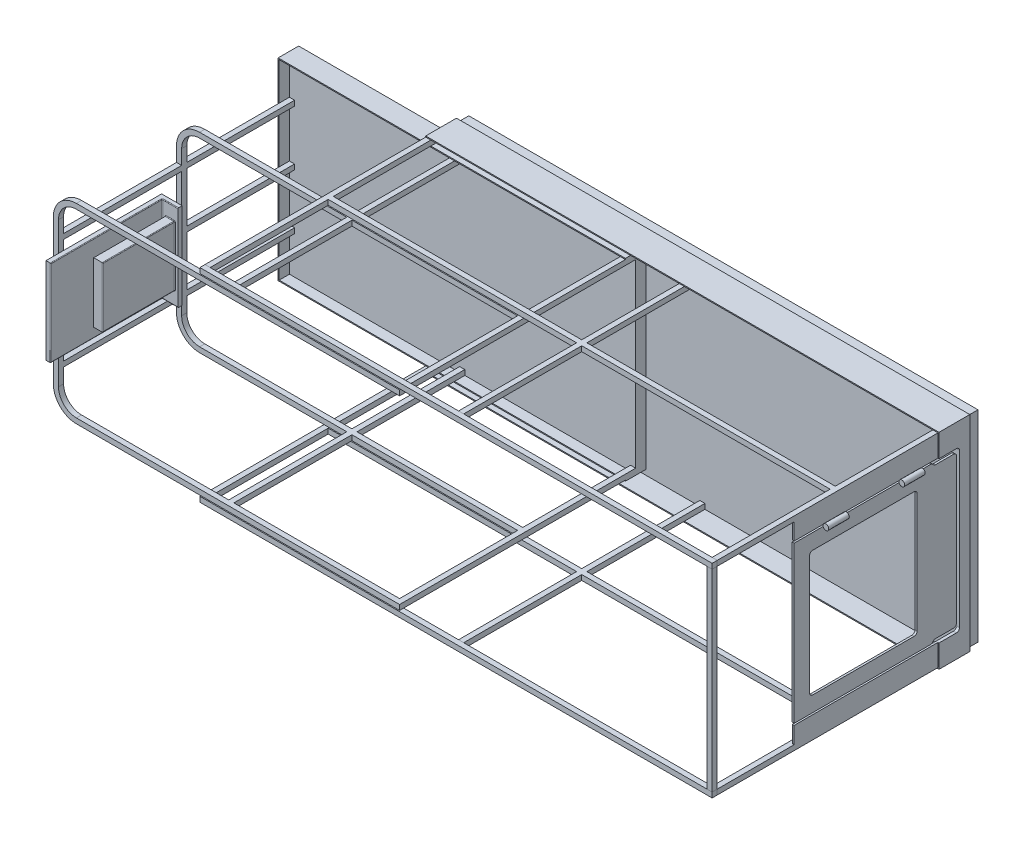
SolidWorks part; units mm, degrees
ref_plane "Front Plane" through (0, 0, 0) normal (0, 0, 1) x (1, 0, 0)
ref_plane "Top Plane" through (0, 0, 0) normal (0, 1, 0) x (1, 0, 0)
ref_plane "Right Plane" through (0, 0, 0) normal (1, 0, 0) x (0, 0, -1)
sketch "Sketch1" plane through (0, 0, 0) normal (0, 0, 1) x (1, 0, 0)
  line L1 (-1250, -500) -> (1250, -500)
  line L2 (-1250, -500) -> (-1250, 500)
  line L3 (-1250, 500) -> (1250, 500)
  line L4 (1250, -500) -> (1250, 500)
  line L5 (-1250, -500) -> (1250, 500) construction
  line L6 (-1250, 500) -> (1250, -500) construction
  point P0 (0, 0)
  dimension "D1" = 2500
  dimension "D2" = 1000
extrude "Boss-Extrude1" add sketch "Sketch1" along normal blind 150
sketch "Sketch2" plane through (0, 0, 0) normal (0, 0, 1) x (1, 0, 0)
  line L0 (1250, -500) -> (1250, 500) construction
  line L1 (-1250, -16.92) -> (1250, -16.92)
  line L2 (-1250, -16.92) -> (-1250, 16.92)
  line L3 (-1250, 16.92) -> (1250, 16.92)
  line L4 (1250, -16.92) -> (1250, 16.92)
  line L5 (-1250, -16.92) -> (1250, 16.92) construction
  line L6 (-1250, 16.92) -> (1250, -16.92) construction
  point P0 (0, 0)
  dimension "D1" = 33.84
extrude "Boss-Extrude2" add sketch "Sketch2" against normal blind 300
sketch "Sketch6" plane through (0, -16.92, 0) normal (0, -1, 0) x (1, 0, 0)
  line L0 (1250, -300) -> (1250, 0) construction
  line L1 (-1250, 0) -> (1250, 0) construction
  circle A0 centre (1017.6, -85.12) radius 20.5
  dimension "D1" = 41
  dimension "D2" = 232.4
  dimension "D3" = 85.12
extrude "Cut-Extrude3" cut sketch "Sketch6" against normal through all
sketch "Sketch7" plane through (0, -16.92, 0) normal (0, -1, 0) x (1, 0, 0)
  line L0 (1114.79, 0) -> (1096.4328, -57.4168)
  line L1 (-1250, 0) -> (1250, 0) construction
  line L2 (-1250, 0) -> (1250, 0) construction
  line L3 (1250, -300) -> (1250, 0) construction
  line L4 (756.61, 0) -> (976.3781, -157.8031)
  line L6 (1114.79, 0) -> (1250, 0)
  line L7 (-1250, -315.6062) -> (1250, -315.6062)
  line L8 (-1250, -315.6062) -> (-1250, 0)
  line L9 (-1250, 0) -> (756.61, 0)
  line L10 (1250, -315.6062) -> (1250, 0)
  line L11 (-1250, -315.6062) -> (1250, 0) construction
  line L12 (-1250, 0) -> (1250, -315.6062) construction
  arc A0 (976.3781, -157.8031) -> (1096.4328, -57.4168) centre (1017.6, -85.12) ccw
  point P12 (0, -157.8031)
  dimension "D1" = 60.28
  dimension "D2" = 72.27
  dimension "D3" = 135.21
  dimension "D5" = 358.18
  dimension "D6" = 35.68
extrude "Cut-Extrude5" cut sketch "Sketch7" against normal through all
sketch "Sketch8" plane through (0, 0, 150) normal (0, 0, 1) x (1, 0, 0)
  line L0 (1250, -500) -> (1250, 500) construction
  line L1 (-1245, -495) -> (1245, -495)
  line L2 (-1245, -495) -> (-1245, 495)
  line L3 (-1245, 495) -> (1245, 495)
  line L4 (1245, -495) -> (1245, 495)
  line L5 (-1245, -495) -> (1245, 495) construction
  line L6 (-1245, 495) -> (1245, -495) construction
  line L7 (-1250, -500) -> (1250, -500) construction
  line L8 (-1250, 500) -> (-1250, -500) construction
  line L9 (1250, 500) -> (-1250, 500) construction
  line L10 (1250, -500) -> (1250, 500)
  line L11 (-1250, -500) -> (1250, -500)
  line L12 (-1250, 500) -> (-1250, -500)
  line L13 (1250, 500) -> (-1250, 500)
  point P0 (0, 0)
  dimension "D1" = 5
  dimension "D2" = 5
extrude "Cut-Extrude6" cut sketch "Sketch8" against normal blind 100 contours L2 L1 L4 L3
sketch "Sketch9" plane through (-1250, 0, 0) normal (-1, 0, 0) x (0, 0, 1)
  line L0 (150, 500) -> (150, -500) construction
  line L1 (50, -495) -> (150, -495)
  line L2 (50, -495) -> (50, 495)
  line L3 (50, 495) -> (150, 495)
  line L4 (150, -495) -> (150, 495)
  line L5 (50, -495) -> (150, 495) construction
  line L6 (50, 495) -> (150, -495) construction
  point P0 (100, 0)
  dimension "D1" = 990
  dimension "D2" = 100
extrude "Cut-Extrude7" cut sketch "Sketch9" against normal up to surface (5 mm away) up to face at (-1245, 0, 100)
sketch "Sketch10" plane through (0, 0, 50) normal (0, 0, 1) x (1, 0, 0)
  line L0 (-15, 495) -> (10, 495)
  line L1 (-1250, 495) -> (-1225, 495)
  line L2 (-1250, 495) -> (-1250, 470)
  line L3 (-1250, 470) -> (-1225, 470)
  line L4 (-1225, 495) -> (-1225, 470)
  line L5 (-15, 495) -> (-15, 470)
  line L6 (-15, 470) -> (10, 470)
  line L7 (10, 495) -> (10, 470)
  line L8 (1220, 495) -> (1245, 495)
  line L9 (1220, 495) -> (1220, 470)
  line L10 (1220, 470) -> (1245, 470)
  line L11 (1245, 495) -> (1245, 470)
  line L12 (-15, -470) -> (10, -470)
  line L13 (-15, -470) -> (-15, -495)
  line L14 (-15, -495) -> (10, -495)
  line L15 (10, -470) -> (10, -495)
  line L16 (1220, -470) -> (1245, -470)
  line L17 (1220, -470) -> (1220, -495)
  line L18 (1220, -495) -> (1245, -495)
  line L19 (1245, -470) -> (1245, -495)
  line L20 (-1250, -470) -> (-1225, -470)
  line L21 (-1250, -470) -> (-1250, -495)
  line L22 (-1250, -495) -> (-1225, -495)
  line L23 (-1225, -470) -> (-1225, -495)
  dimension "D1" = 25
  dimension "D2" = 25
  dimension "D3" = 3
  dimension "D4" = 2
extrude "Boss-Extrude3" add sketch "Sketch10" along normal blind 1200
sketch "Sketch11" plane through (0, 0, 50) normal (0, 0, 1) x (1, 0, 0)
  line L1 (-277.22, 470) -> (-1968.62, 470)
  line L2 (-277.22, 470) -> (-277.22, -470)
  line L3 (-277.22, -470) -> (-1968.62, -470)
  line L4 (-1968.62, 470) -> (-1968.62, -470)
  line L6 (-1250, 470) -> (-1250, -470) construction
  line L10 (-1250, 470) -> (-1225, 470) construction
  line L11 (-1225, -470) -> (-1250, -470) construction
  dimension "D1" = 1691.4
  dimension "D2" = 718.62
extrude "Boss-Extrude4" add sketch "Sketch11" along normal blind 50
sketch "Sketch12" plane through (0, 0, 100) normal (0, 0, 1) x (1, 0, 0)
  line L0 (-1968.62, 470) -> (-1968.62, -470) construction
  line L1 (-1963.62, 465) -> (-277.22, 465)
  line L2 (-1963.62, 465) -> (-1963.62, -465)
  line L3 (-1963.62, -465) -> (-277.22, -465)
  line L5 (-1963.62, 465) -> (-277.22, -465) construction
  line L6 (-1963.62, -465) -> (-277.22, 465) construction
  line L7 (-1250, -470) -> (-1225, -470) construction
  line L8 (-1968.62, -470) -> (-1250, -470) construction
  line L9 (-1225, -470) -> (-277.22, -470) construction
  line L10 (-277.22, -470) -> (-277.22, 470) construction
  line L11 (-277.22, 470) -> (-1225, 470) construction
  line L12 (-1225, 470) -> (-1250, 470) construction
  line L13 (-1250, 470) -> (-1968.62, 470) construction
  line L14 (-1968.62, 470) -> (-1968.62, -470)
  line L15 (-1250, -470) -> (-1225, -470)
  line L16 (-1968.62, -470) -> (-1250, -470)
  line L17 (-1225, -470) -> (-277.22, -470)
  line L18 (-277.22, -470) -> (-277.22, -465)
  line L19 (-277.22, 470) -> (-1225, 470)
  line L20 (-1225, 470) -> (-1250, 470)
  line L21 (-1250, 470) -> (-1968.62, 470)
  line L22 (-277.22, 465) -> (-277.22, 470)
  point P0 (-1120.42, 0)
  dimension "D1" = 5
  dimension "D2" = 5
  dimension "D3" = 5
extrude "Boss-Extrude5" add sketch "Sketch12" along normal up to surface (50 mm away) up to face at (136.6667, 0, 150)
sketch "Sketch13" plane through (0, 0, 100) normal (0, 0, 1) x (1, 0, 0)
  line L0 (-1109.42, 440) -> (-1134.42, 440)
  line L1 (-277.22, 465) -> (-302.22, 465)
  line L2 (-277.22, 465) -> (-277.22, 440)
  line L3 (-277.22, 440) -> (-302.22, 440)
  line L4 (-302.22, 465) -> (-302.22, 440)
  line L5 (-1134.42, 465) -> (-1134.42, 440)
  line L6 (-1109.42, 465) -> (-1134.42, 465)
  line L7 (-1109.42, 465) -> (-1109.42, 440)
  line L8 (-1109.42, -465) -> (-1134.42, -465)
  line L9 (-1134.42, -440) -> (-1134.42, -465)
  line L10 (-1109.42, -440) -> (-1134.42, -440)
  line L11 (-1109.42, -440) -> (-1109.42, -465)
  line L12 (-277.22, -465) -> (-302.22, -465)
  line L13 (-302.22, -440) -> (-302.22, -465)
  line L14 (-277.22, -440) -> (-302.22, -440)
  line L15 (-277.22, -440) -> (-277.22, -465)
  line L16 (0, 0) -> (-2311.2955, 0) construction
  line L17 (-1963.62, 465) -> (-1963.62, -465) construction
  line L18 (-1963.62, -256.43) -> (-1938.62, -256.43)
  line L19 (-1963.62, -256.43) -> (-1963.62, -281.43)
  line L20 (-1963.62, -281.43) -> (-1938.62, -281.43)
  line L21 (-1938.62, -256.43) -> (-1938.62, -281.43)
  line L22 (-1938.62, 256.43) -> (-1938.62, 281.43)
  line L23 (-1963.62, 281.43) -> (-1938.62, 281.43)
  line L24 (-1963.62, 256.43) -> (-1963.62, 281.43)
  line L25 (-1963.62, 256.43) -> (-1938.62, 256.43)
  dimension "D1" = 25
  dimension "D2" = 25
  dimension "D5" = 25
  dimension "D6" = 25
  dimension "D7" = 512.86
  dimension "D3" = 2
  dimension "D4" = 2
extrude "Boss-Extrude6" add sketch "Sketch13" along normal up to surface (1150 mm away) up to face at (-1237.5, -482.5, 1250)
sketch "Sketch14" plane through (0, 0, 1250) normal (0, 0, 1) x (1, 0, 0)
  line L0 (-1963.62, 281.43) -> (-1963.62, 465) construction
  line L1 (-1250, -470) -> (1245, -470)
  line L2 (-1250, -470) -> (-1250, -495)
  line L3 (-1250, -495) -> (1245, -495)
  line L4 (1245, -470) -> (1245, -495)
  line L5 (-1250, 495) -> (1245, 495)
  line L6 (-1250, 495) -> (-1250, 470)
  line L7 (-1250, 470) -> (1245, 470)
  line L8 (1245, 495) -> (1245, 470)
  line L9 (-277.22, 465) -> (-1851.12, 465)
  line L10 (-277.22, 465) -> (-277.22, 440)
  line L11 (-277.22, 440) -> (-1851.12, 440)
  line L14 (-277.22, -465) -> (-1851.12, -465)
  line L15 (-277.22, -465) -> (-277.22, -440)
  line L16 (-277.22, -440) -> (-1851.12, -440)
  line L20 (-1963.62, -352.5) -> (-1963.62, 352.5)
  line L22 (-1938.62, -352.5) -> (-1938.62, 352.5)
  arc A0 (-1851.12, 440) -> (-1938.62, 352.5) centre (-1851.12, 352.5) ccw
  arc A1 (-1938.62, -352.5) -> (-1851.12, -440) centre (-1851.12, -352.5) ccw
  arc A2 (-1963.62, -352.5) -> (-1851.12, -465) centre (-1851.12, -352.5) ccw
  arc A3 (-1963.62, 352.5) -> (-1851.12, 465) centre (-1851.12, 352.5) cw
  point P37 (-1963.62, 465)
  dimension "D1" = 87.5
  dimension "D2" = 112.5
extrude "Boss-Extrude7" add sketch "Sketch14" against normal blind 25 separate body
pattern_linear "LPattern1" count 2 spacing 600 along (0, 0, -1) of bodies 116 115 117
sketch "Sketch15" plane through (0, 0, 50) normal (0, 0, 1) x (1, 0, 0)
  line L0 (0, 0) -> (1570.6442, 0) construction
  line L1 (1245, 470) -> (1235.42, 470)
  line L2 (1245, 470) -> (1245, 388.56)
  line L3 (1245, 388.56) -> (1235.42, 388.56)
  line L4 (1235.42, 470) -> (1235.42, 388.56)
  line L5 (1235.42, -470) -> (1235.42, -388.56)
  line L6 (1245, -388.56) -> (1235.42, -388.56)
  line L7 (1245, -470) -> (1245, -388.56)
  line L8 (1245, -470) -> (1235.42, -470)
  dimension "D1" = 81.44
  dimension "D2" = 9.58
extrude "Boss-Extrude8" add sketch "Sketch15" along normal blind 800
sketch "Sketch16" plane through (1250, 0, 0) normal (1, 0, 0) x (0, 0, -1)
  line L0 (-150, -500) -> (-150, 500) construction
  line L1 (-150, 388.56) -> (-50, 388.56)
  line L2 (-150, 388.56) -> (-150, -388.56)
  line L3 (-150, -388.56) -> (-50, -388.56)
  line L4 (-50, 388.56) -> (-50, -388.56)
  line L5 (-850, -388.56) -> (-150, -388.56) construction
  line L6 (-850, 388.56) -> (-150, 388.56) construction
  dimension "D1" = 100
extrude "Cut-Extrude8" cut sketch "Sketch16" against normal blind 800
sketch "Sketch17" plane through (0, 470, 0) normal (0, -1, 0) x (1, 0, 0)
  line L0 (-1250, 1225) -> (1245, 1225) construction
  line L1 (1245, 1250) -> (1220, 1250)
  line L2 (1245, 1250) -> (1245, 1225)
  line L3 (1245, 1225) -> (1220, 1225)
  line L4 (1220, 1250) -> (1220, 1225)
  line L5 (1220, 1250) -> (1220, 650) construction
extrude "Boss-Extrude9" add sketch "Sketch17" along normal up to surface (940 mm away) separate body up to face at (110.0382, -470, 672.7273)
sketch "Sketch18" plane through (1245, 0, 0) normal (1, 0, 0) x (0, 0, -1)
  line L0 (-50, 0) -> (-923.4895, 0) construction
  line L1 (-50, -388.56) -> (-50, 388.56) construction
  line L2 (-850, -380.06) -> (-850, 380.06)
  line L3 (-850, 380.06) -> (-176.46, 380.06)
  line L4 (-176.46, 380.06) -> (-176.46, 366.82)
  line L5 (-176.46, 366.82) -> (-59.3, 366.82)
  line L6 (-59.3, 366.82) -> (-59.3, -366.82)
  line L7 (-850, 388.56) -> (-850, 470) construction
  line L8 (-850, 388.56) -> (-150, 388.56) construction
  line L9 (-176.46, -366.82) -> (-59.3, -366.82)
  line L10 (-176.46, -380.06) -> (-176.46, -366.82)
  line L11 (-850, -380.06) -> (-176.46, -380.06)
  line L13 (-775, -305.06) -> (-251.46, -305.06)
  line L14 (-775, -305.06) -> (-775, 305.06)
  line L15 (-775, 305.06) -> (-251.46, 305.06)
  line L16 (-251.46, -305.06) -> (-251.46, 305.06)
  point P16 (-59.3, 0)
  point P19 (-850, 0)
  dimension "D1" = 8.5
  dimension "D2" = 117.16
  dimension "D3" = 673.54
  dimension "D4" = 13.24
  dimension "D5" = 75
  dimension "D6" = 75
  dimension "D7" = 75
  dimension "D8" = 523.54
  dimension "D9" = 523.54
extrude "Boss-Extrude10" add sketch "Sketch18" against normal blind 10 separate body
sketch "Sketch19" plane through (-1963.62, 0, 0) normal (-1, 0, 0) x (0, 0, 1)
  line L0 (1250, 352.5) -> (1250, -352.5) construction
  line L1 (1310.7, 210.155) -> (747.59, 210.155)
  line L2 (1310.7, 210.155) -> (1310.7, -210.155)
  line L3 (1310.7, -210.155) -> (747.59, -210.155)
  line L4 (747.59, 210.155) -> (747.59, -210.155)
  point P7 (1310.7, 0)
  dimension "D1" = 420.31
  dimension "D2" = 563.11
  dimension "D3" = 60.7
sketch "Sketch21" plane through (-1938.62, 0, 0) normal (1, 0, 0) x (0, 0, -1)
  line L0 (-747.59, 210.155) -> (-747.59, -210.155) construction
  line L1 (-1310.7, -210.155) -> (-747.59, -210.155) construction
  line L2 (-1310.7, 210.155) -> (-1310.7, -210.155) construction
  line L3 (-1310.7, 210.155) -> (-747.59, 210.155) construction
  line L4 (-747.59, 210.155) -> (-747.59, -210.155)
  line L5 (-1310.7, -210.155) -> (-747.59, -210.155)
  line L6 (-1310.7, 210.155) -> (-1310.7, -210.155)
  line L7 (-1310.7, 210.155) -> (-747.59, 210.155)
extrude "Boss-Extrude12" add sketch "Sketch21" along normal blind 100
sketch "Sketch22" plane through (0, 0, 100) normal (0, 0, 1) x (1, 0, 0)
  line L0 (-1963.62, 256.43) -> (-1963.62, -256.43) construction
  line L1 (-1963.62, 12.5) -> (-1938.62, 12.5)
  line L2 (-1963.62, 12.5) -> (-1963.62, -12.5)
  line L3 (-1963.62, -12.5) -> (-1938.62, -12.5)
  line L4 (-1938.62, 12.5) -> (-1938.62, -12.5)
  line L5 (0, 0) -> (-2844.8791, 0) construction
  point P9 (-1938.62, 0)
  dimension "D1" = 25
  dimension "D2" = 25
extrude "Boss-Extrude13" add sketch "Sketch22" along normal up to surface (1125 mm away) up to face at (-1946.9533, 0, 1225)
sketch "Sketch23" plane through (0, 0, 1310.7) normal (0, 0, 1) x (1, 0, 0)
  line L0 (-1838.62, -210.155) -> (-1938.62, -210.155) construction
  line L1 (-1838.62, 210.155) -> (-1915.62, 210.155)
  line L2 (-1838.62, 210.155) -> (-1838.62, -210.155)
  line L3 (-1838.62, -210.155) -> (-1915.62, -210.155)
  line L4 (-1915.62, 210.155) -> (-1915.62, -210.155)
  dimension "D1" = 77
extrude "Cut-Extrude9" cut sketch "Sketch23" against normal blind 543
sketch "Sketch24" plane through (0, 0, 767.7) normal (0, 0, 1) x (1, 0, 0)
  line L0 (0, 0) -> (-3708.5, 0) construction
  line L1 (-1838.62, -210.155) -> (-1838.62, 210.155) construction
  line L2 (-1898.08, 146.67) -> (-1854.25, 146.67)
  line L3 (-1898.08, 146.67) -> (-1898.08, -146.67)
  line L4 (-1898.08, -146.67) -> (-1854.25, -146.67)
  line L5 (-1854.25, 146.67) -> (-1854.25, -146.67)
  point P7 (-1854.25, 0)
  dimension "D1" = 15.63
  dimension "D2" = 43.83
  dimension "D3" = 293.34
extrude "Boss-Extrude14" add sketch "Sketch24" along normal blind 351
sketch "Sketch25" plane through (0, 0, 0) normal (0, 0, -1) x (-1, 0, 0)
  line L12 (-1240, -500) -> (-1240, 500)
  line L13 (1240, -490) -> (-1250, -490)
  line L14 (1240, 490) -> (1240, -490)
  line L15 (-1250, 490) -> (1240, 490)
  line L16 (1240, -490) -> (-1240, -490)
  line L17 (1240, 490) -> (1240, -490)
  line L18 (-1240, 490) -> (1240, 490)
  line L19 (-1240, -490) -> (-1240, 490)
  line L20 (1230, 480) -> (1230, -480)
  line L21 (1230, -480) -> (-1230, -480)
  line L23 (-1230, 480) -> (1230, 480)
  line L24 (-1250, 480) -> (1230, 480) construction
  line L25 (1240, -490) -> (-1250, -490) construction
  line L28 (-1250, 490) -> (1240, 490) construction
  line L29 (1230, -480) -> (-1250, -480) construction
  line L30 (-1230, -480) -> (-1230, 480)
  dimension "D1" = 10
  dimension "D2" = 10
  dimension "D3" = 10
extrude "Boss-Extrude15" add sketch "Sketch25" along normal blind 50
sketch "Sketch26" plane through (0, 0, 50) normal (0, 0, -1) x (-1, 0, 0)
  line L0 (1250, 470) -> (1250, -470) construction
  line L1 (1250, 452) -> (1950.62, 452)
  line L2 (1250, 452) -> (1250, -452)
  line L3 (1250, -452) -> (1950.62, -452)
  line L4 (1950.62, 452) -> (1950.62, -452)
  line L5 (1250, 470) -> (1968.62, 470) construction
  line L6 (1968.62, 470) -> (1968.62, -470) construction
  line L7 (1968.62, -470) -> (1250, -470) construction
  dimension "D1" = 18
  dimension "D2" = 18
  dimension "D3" = 18
extrude "Cut-Extrude10" cut sketch "Sketch26" against normal blind 40
ref_plane "Plane1" through (0, 0, 710) normal (0, 0, 1) x (1, 0, 0)
sketch "Sketch27" plane through (0, 0, 710) normal (0, 0, 1) x (1, 0, 0)
  line L2 (1245, 388.56) -> (1245, 470) construction
  line L3 (1245, 380.06) -> (1245, -380.06) construction
  line L4 (1235.42, 388.56) -> (1245, 388.56) construction
  circle A0 centre (1259, 384.31) radius 14
  dimension "D1" = 28
  dimension "D2" = 4.25
extrude "Boss-Extrude16" add sketch "Sketch27" against normal blind 100
pattern_linear "LPattern4" count 2 spacing 370 along (0, 0, -1) of bodies 134
sketch "Sketch28" plane through (0, -500, 0) normal (0, -1, 0) x (1, 0, 0)
  line L0 (-1070.1302, 18.3635) -> (1070.1302, 18.3635) construction
  text T0 "ENG-AMINE" font "Ebrima" height in points 400
  point P2 (0, 18.3635)
extrude "Cut-Extrude11" cut sketch "Sketch28" against normal blind 0.5
fillet "Fillet1" radius 15 4 edges at (1240, 305.06, 775) (1240, -305.06, 775) (1240, -305.06, 251.46) (1240, 305.06, 251.46)
fillet "Fillet2" radius 3 12 edges at (-1877.12, 210.155, 767.7) (-1877.12, -210.155, 767.7) (-1876.165, -146.67, 767.7) (-1876.165, 146.67, 767.7) (-1915.62, 210.155, 1039.2) (-1915.62, 0, 767.7) (-1915.62, -210.155, 1039.2) (-1915.62, 0, 1310.7) (-1854.25, -146.67, 943.2) (-1854.25, 0, 1118.7) (-1854.25, 146.67, 943.2) (-1854.25, 0, 767.7)
fillet "Fillet4" radius 15 4 edges at (1240, -366.82, 59.3) (1240, -366.82, 176.46) (1240, 366.82, 59.3) (1240, 366.82, 176.46)
fillet "Fillet5" radius 15 2 edges at (1240, 380.06, 176.46) (1240, -380.06, 176.46)
fillet "Fillet6" radius 15 2 edges at (1242.71, -388.56, 50) (1242.71, 388.56, 50)
